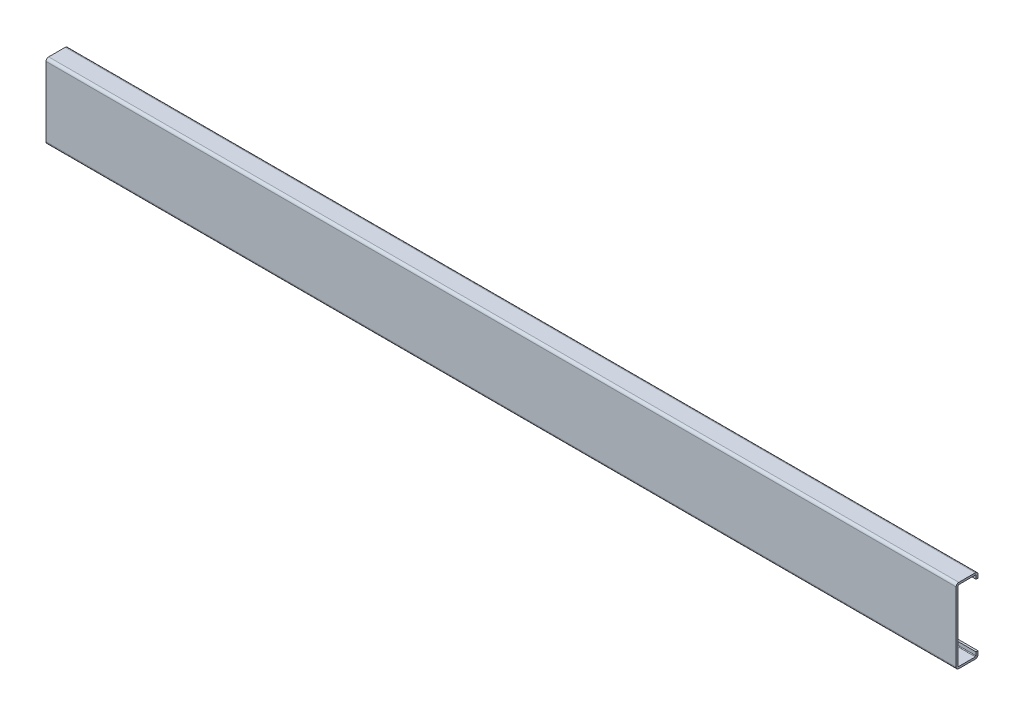
SolidWorks part; units mm, degrees
ref_plane "Спереди" through (0, 0, 0) normal (0, 0, 1) x (1, 0, 0)
ref_plane "Сверху" through (0, 0, 0) normal (0, 1, 0) x (1, 0, 0)
ref_plane "Справа" through (0, 0, 0) normal (1, 0, 0) x (0, 0, -1)
sketch "Эскиз1" plane through (0, 0, 0) normal (1, 0, 0) x (0, 0, -1)
  line L0 (0, -21) -> (0, 21)
  line L1 (-12.4481, 0) -> (26.4522, 0) construction
  line L2 (1, 22) -> (11, 22)
  line L3 (12, 21) -> (12, 19)
  line L4 (12, -21) -> (12, -19)
  line L5 (1, -22) -> (11, -22)
  arc A0 (11, 22) -> (12, 21) centre (11, 21) cw
  arc A1 (0, 21) -> (1, 22) centre (1, 21) cw
  arc A2 (0, -21) -> (1, -22) centre (1, -21) ccw
  arc A3 (11, -22) -> (12, -21) centre (11, -21) ccw
  point P19 (0, 0)
  dimension "D1" = 1
extrude "Вытянуть-Тонкостенный1" add sketch "Эскиз1" along normal blind 550 thin thin type mid plane wall 1.2
